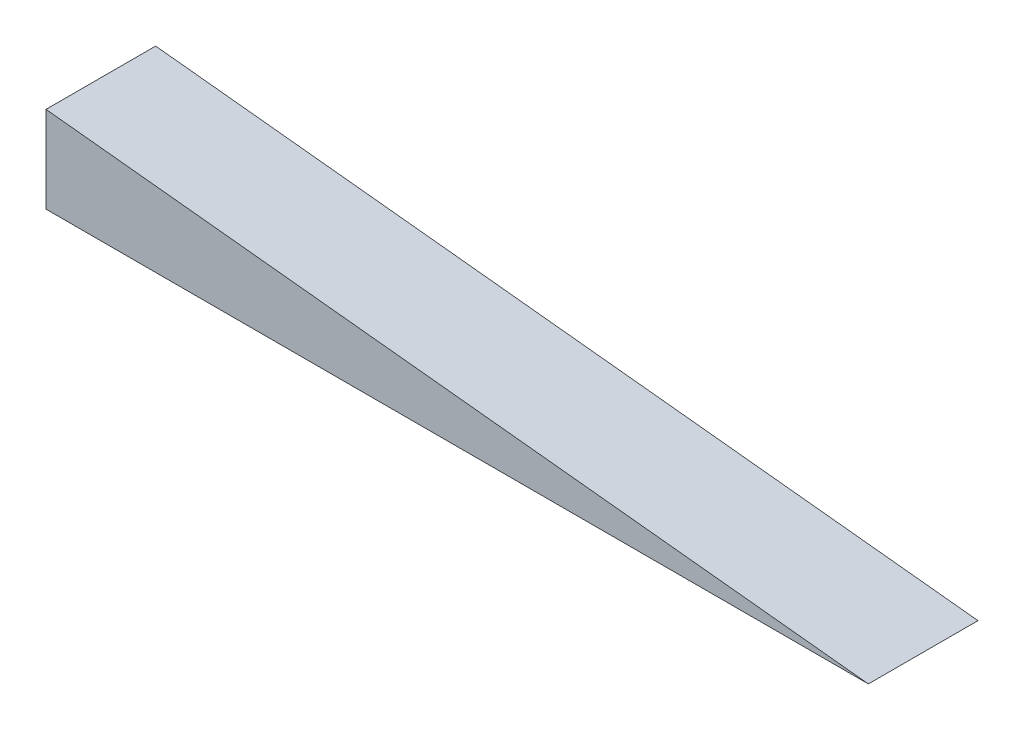
SolidWorks part; units mm, degrees
ref_plane "Front Plane" through (0, 0, 0) normal (0, 0, 1) x (1, 0, 0)
ref_plane "Top Plane" through (0, 0, 0) normal (0, 1, 0) x (1, 0, 0)
ref_plane "Right Plane" through (0, 0, 0) normal (1, 0, 0) x (0, 0, -1)
sketch "Sketch1" plane through (0, 0, 0) normal (0, 0, 1) x (1, 0, 0)
  line L0 (-50.1477, 0) -> (99.8523, 0)
  line L1 (55, 0) -> (-55, 0) construction
  line L2 (99.8523, 0) -> (-50.1477, 15.7656)
  line L3 (-50.1477, 15.7656) -> (-50.1477, 0)
  dimension "D1" = 150
  dimension "D2" = 6
extrude "Boss-Extrude1" add sketch "Sketch1" along normal mid plane 20
